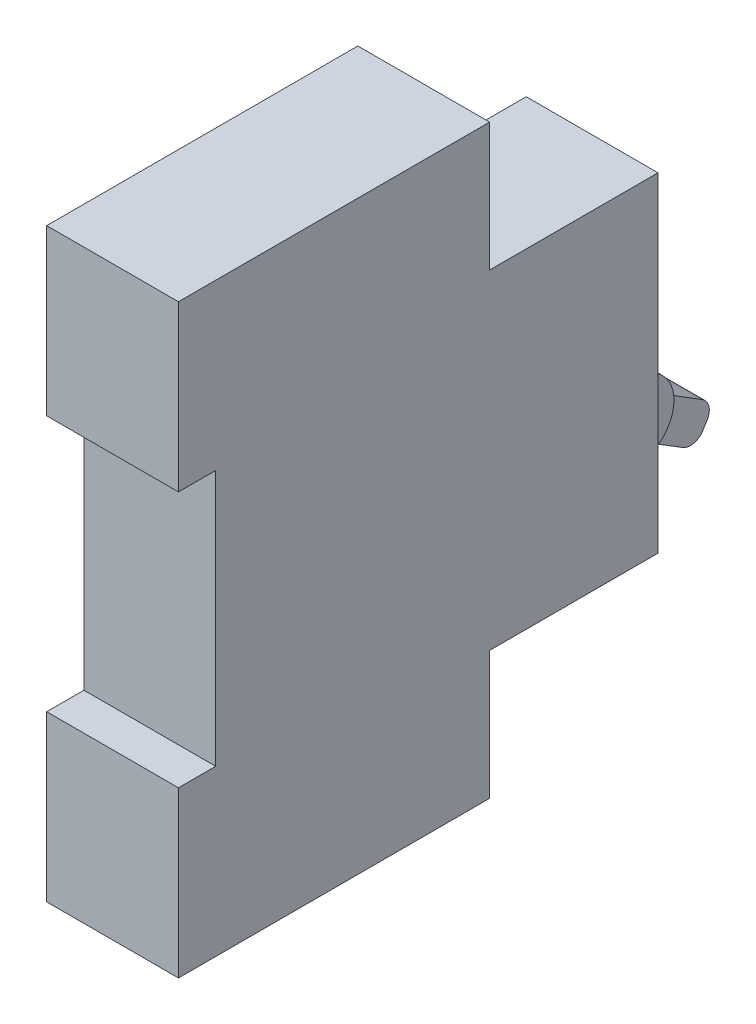
SolidWorks part; units mm, degrees
ref_plane "前视基准面" through (0, 0, 0) normal (0, 0, 1) x (1, 0, 0)
ref_plane "上视基准面" through (0, 0, 0) normal (0, 1, 0) x (1, 0, 0)
ref_plane "右视基准面" through (0, 0, 0) normal (1, 0, 0) x (0, 0, -1)
sketch "草图1" plane through (0, 0, 0) normal (1, 0, 0) x (0, 0, -1)
  line L0 (0, 52.9257) -> (0, -65.8977) construction
  line L1 (-128.0336, 0) -> (98.198, 0) construction
  line L2 (0, 17.5) -> (0, 40)
  line L3 (0, 40) -> (42.5, 40)
  line L4 (42.5, 40) -> (42.5, 22.5)
  line L5 (42.5, 22.5) -> (65.5, 22.5)
  line L6 (65.5, 22.5) -> (65.5, -22.5)
  line L7 (0, 17.5) -> (5.085, 17.5)
  line L8 (5.085, 17.5) -> (5.085, -17.5)
  line L9 (0, -17.5) -> (5.085, -17.5)
  line L10 (42.5, -22.5) -> (65.5, -22.5)
  line L11 (42.5, -40) -> (42.5, -22.5)
  line L12 (0, -40) -> (42.5, -40)
  line L13 (0, -17.5) -> (0, -40)
  point P14 (5.085, 0)
  point P16 (65.5, 0)
  dimension "D1" = 80
  dimension "D2" = 35
  dimension "D3" = 42.5
  dimension "D4" = 65.5
  dimension "D5" = 45
extrude "凸台-拉伸1" add sketch "草图1" along normal blind 9 and the other way blind 9
sketch "草图2" plane through (0, 0, 0) normal (1, 0, 0) x (0, 0, -1)
  line L0 (-33.159, 0) -> (81.2781, 0) construction
  line L1 (65.5, -22.5) -> (65.5, 22.5) construction
  line L2 (65.5, -3.3078) -> (65.5, -13.6686)
  arc A0 (65.5, -13.6686) -> (65.5, -3.3078) centre (65.5, -8.4882) ccw
extrude "凸台-拉伸2" add sketch "草图2" along normal blind 6 and the other way blind 6
sketch "草图3" plane through (0, 0, 0) normal (1, 0, 0) x (0, 0, -1)
  line L0 (65.5, -8.4882) -> (80.5122, -17.8133) construction
  line L1 (65.5, -3.3078) -> (65.5, -13.6686) construction
  line L2 (69.816, -8.1688) -> (67.1264, -12.4988)
  line L3 (67.1264, -12.4988) -> (75.5764, -17.7478)
  line L4 (69.816, -8.1688) -> (78.2661, -13.4177)
  line L5 (78.2661, -13.4177) -> (75.5764, -17.7478)
  point P9 (68.4712, -10.3338)
extrude "凸台-拉伸3" add sketch "草图3" along normal blind 4 and the other way blind 4
fillet "圆角2" radius 2 2 edges at (0, -17.7478, -75.5764) (0, -13.4177, -78.2661)
